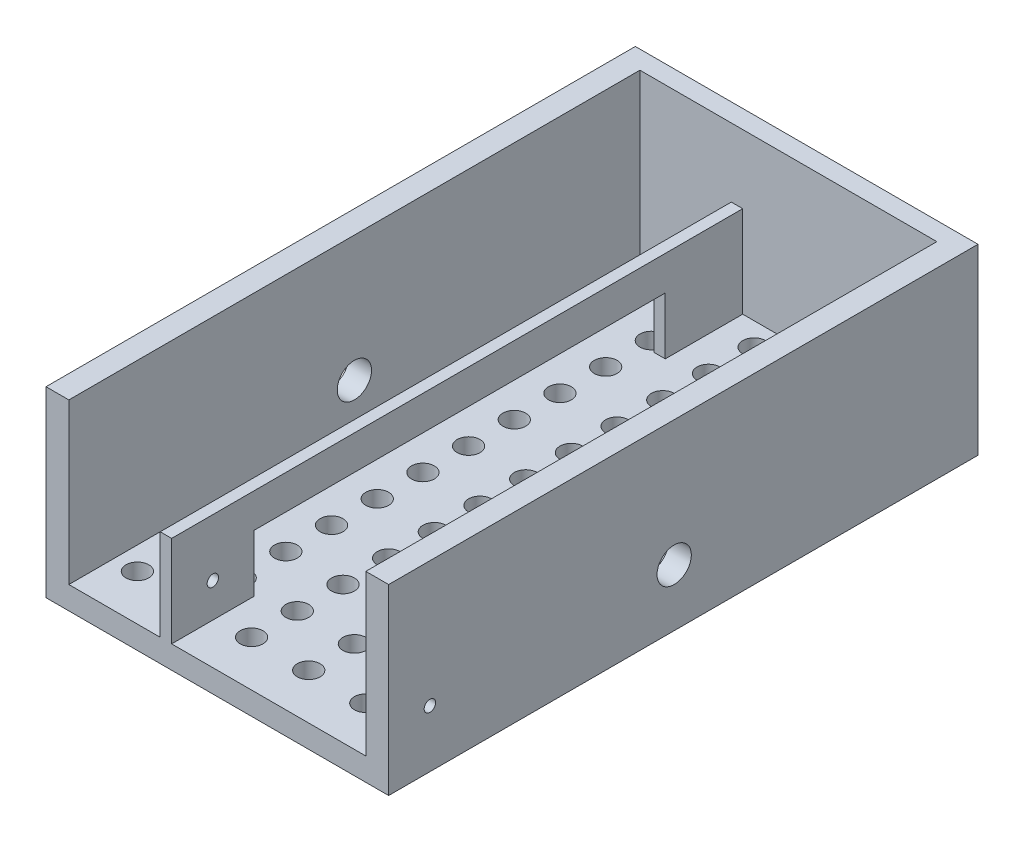
SolidWorks part; units mm, degrees
ref_plane "前基準面" through (0, 0, 0) normal (0, 0, 1) x (1, 0, 0)
ref_plane "上基準面" through (0, 0, 0) normal (0, 1, 0) x (1, 0, 0)
ref_plane "右基準面" through (0, 0, 0) normal (1, 0, 0) x (0, 0, -1)
sketch "草圖4" plane through (0, 0, 0) normal (0, 1, 0) x (1, 0, 0)
  line L1 (-75, 125) -> (75, 125)
  line L2 (-75, 125) -> (-75, -125)
  line L3 (-75, -125) -> (75, -125)
  line L4 (75, 125) -> (75, -125)
  line L5 (-75, 125) -> (75, -125) construction
  line L6 (-75, -125) -> (75, 125) construction
  point P0 (0, 0)
  dimension "D1" = 150
  dimension "D2" = 250
extrude "填料-伸長2" add sketch "草圖4" along normal blind 10
sketch "草圖5" plane through (0, 0, 125) normal (0, 0, 1) x (1, 0, 0)
  line L0 (-75, 0) -> (75, 0) construction
  line L1 (-75, 0) -> (75, 0)
  line L2 (-75, 0) -> (-75, 80)
  line L3 (-75, 80) -> (-65, 80)
  line L4 (-65, 80) -> (-65, 10)
  line L5 (-75, 10) -> (75, 10) construction
  line L6 (-65, 10) -> (-25, 10)
  line L7 (65, 10) -> (65, 80)
  line L8 (65, 80) -> (75, 80)
  line L9 (75, 80) -> (75, 0)
  line L10 (0, -16.5248) -> (0, 113.0975) construction
  line L11 (-20, 10) -> (-20, 50)
  line L12 (-20, 50) -> (-25, 50)
  line L13 (-25, 50) -> (-25, 10)
  line L14 (-20, 10) -> (65, 10)
  dimension "D1" = 10
  dimension "D2" = 80
  dimension "D3" = 5
  dimension "D4" = 40
  dimension "D5" = 85
extrude "填料-伸長3" add sketch "草圖5" against normal up to surface (250 mm away) up to face at (0, 5, -125)
sketch "草圖6" plane through (-25, 0, 0) normal (-1, 0, 0) x (0, 0, 1)
  line L1 (-91.0879, 10) -> (88.9121, 10)
  line L2 (-91.0879, 10) -> (-91.0879, 35)
  line L3 (-91.0879, 35) -> (88.9121, 35)
  line L4 (-125, 50) -> (-125, 10)
  line L5 (-125, 10) -> (125, 10)
  line L6 (125, 10) -> (125, 50)
  line L7 (125, 50) -> (-125, 50)
  line L8 (-125, 50) -> (-125, 10) construction
  line L9 (-125, 10) -> (125, 10) construction
  line L10 (125, 10) -> (125, 50) construction
  line L11 (125, 50) -> (-125, 50) construction
  line L12 (88.9121, 10) -> (88.9121, 35)
  dimension "D2" = 180
  dimension "D3" = 25
  dimension "D1" = 0
extrude "除料-伸長1" cut sketch "草圖6" against normal up to next
sketch "草圖7" plane through (0, 0, -125) normal (0, 0, -1) x (-1, 0, 0)
  line L0 (75, 80) -> (75, 0) construction
  line L1 (-75, 0) -> (75, 0)
  line L2 (-75, 0) -> (-75, 80)
  line L3 (-75, 80) -> (75, 80)
  line L4 (75, 0) -> (75, 80)
  line L6 (-65, 80) -> (-75, 80) construction
extrude "填料-伸長4" add sketch "草圖7" along normal blind 8
sketch "草圖8" plane through (0, 10, 0) normal (0, 1, 0) x (1, 0, 0)
  line L0 (-156.4323, 0) -> (126.5721, 0) construction
  line L1 (-22.5, 91.0879) -> (-22.5, -96.7969) construction
  line L4 (-25, -88.9121) -> (-20, -88.9121)
  line L5 (-25, 91.0879) -> (-25, -88.9121)
  line L6 (-20, 91.0879) -> (-25, 91.0879)
  line L7 (-20, -88.9121) -> (-20, 91.0879)
  line L8 (-25, -88.9121) -> (-20, -88.9121) construction
  line L9 (-25, 91.0879) -> (-25, -88.9121) construction
  line L10 (-20, 91.0879) -> (-25, 91.0879) construction
  line L11 (-20, -88.9121) -> (-20, 91.0879) construction
  circle A0 centre (-22.5, 0) radius 2.5
  point P11 (0, 0)
  dimension "D2" = 5
  dimension "D1" = 0
sketch "草圖9" plane through (-75, 0, 0) normal (-1, 0, 0) x (0, 0, 1)
  line L0 (-133, 40) -> (125, 40) construction
  line L1 (-133, 0) -> (-133, 80) construction
  line L2 (125, 80) -> (125, 0) construction
  line L3 (0, 0) -> (0, 80) construction
  line L4 (-133, 80) -> (125, 80) construction
  line L5 (-133, 0) -> (125, 0) construction
  circle A0 centre (0, 25) radius 7.5
  point P13 (0, 0)
  point P14 (0, 20.6437)
  dimension "D1" = 15
  dimension "D2" = 25
extrude "旋轉軸預留孔" cut sketch "草圖9" against normal through all
sketch "草圖10" plane through (-25, 0, 0) normal (-1, 0, 0) x (0, 0, 1)
  line L0 (106.956, 10) -> (106.956, 80) construction
  line L1 (-133, 80) -> (125, 80) construction
  line L8 (88.9121, 35) -> (88.9121, 10)
  line L9 (88.9121, 10) -> (125, 10)
  line L10 (125, 10) -> (125, 50)
  line L11 (125, 50) -> (-125, 50)
  line L12 (-125, 50) -> (-125, 10)
  line L13 (-125, 10) -> (-91.0879, 10)
  line L14 (-91.0879, 10) -> (-91.0879, 35)
  line L15 (-91.0879, 35) -> (88.9121, 35)
  line L16 (88.9121, 35) -> (88.9121, 10) construction
  line L17 (88.9121, 10) -> (125, 10) construction
  line L18 (125, 10) -> (125, 50) construction
  line L19 (125, 50) -> (-125, 50) construction
  line L20 (-125, 50) -> (-125, 10) construction
  line L21 (-125, 10) -> (-91.0879, 10) construction
  line L22 (-91.0879, 10) -> (-91.0879, 35) construction
  line L23 (-91.0879, 35) -> (88.9121, 35) construction
  circle A0 centre (106.956, 25) radius 2.5
  dimension "D2" = 5
  dimension "D3" = 15
  dimension "D1" = 0
extrude "除料-伸長3" cut sketch "草圖10" against normal through all
sketch "草圖11" plane through (0, 10, 0) normal (0, 1, 0) x (1, 0, 0)
  line L0 (65, 105) -> (65, -145) construction
  line L1 (-65, 125) -> (65, 125) construction
  line L2 (-65, 125) -> (-65, -125) construction
  line L3 (-65, -125) -> (65, -125) construction
  line L4 (65, 125) -> (65, -125) construction
  line L5 (65, 85) -> (65, -165) construction
  line L6 (65, 65) -> (65, -185) construction
  line L7 (65, 45) -> (65, -205) construction
  line L8 (65, 25) -> (65, -225) construction
  line L9 (65, 5) -> (65, -245) construction
  line L10 (65, -15) -> (65, -265) construction
  line L11 (65, -35) -> (65, -285) construction
  line L12 (65, -55) -> (65, -305) construction
  line L13 (65, -75) -> (65, -325) construction
  line L14 (65, -95) -> (65, -345) construction
  circle A0 centre (-55, 115) radius 5
  circle A1 centre (-30, 115) radius 5
  circle A2 centre (-5, 115) radius 5
  circle A3 centre (20, 115) radius 5
  circle A4 centre (45, 115) radius 5
  circle A6 centre (70, 115) radius 5 [skipped]
  circle A7 centre (-55, 95) radius 5
  circle A8 centre (-30, 95) radius 5
  circle A9 centre (-5, 95) radius 5
  circle A10 centre (20, 95) radius 5
  circle A11 centre (45, 95) radius 5
  circle A12 centre (-55, 75) radius 5
  circle A13 centre (-30, 75) radius 5
  circle A14 centre (-5, 75) radius 5
  circle A15 centre (20, 75) radius 5
  circle A16 centre (45, 75) radius 5
  circle A17 centre (-55, 55) radius 5
  circle A18 centre (-30, 55) radius 5
  circle A19 centre (-5, 55) radius 5
  circle A20 centre (20, 55) radius 5
  circle A21 centre (45, 55) radius 5
  circle A22 centre (-55, 35) radius 5
  circle A23 centre (-30, 35) radius 5
  circle A24 centre (-5, 35) radius 5
  circle A25 centre (20, 35) radius 5
  circle A26 centre (45, 35) radius 5
  circle A27 centre (-55, 15) radius 5
  circle A28 centre (-30, 15) radius 5
  circle A29 centre (-5, 15) radius 5
  circle A30 centre (20, 15) radius 5
  circle A31 centre (45, 15) radius 5
  circle A32 centre (-55, -5) radius 5
  circle A33 centre (-30, -5) radius 5
  circle A34 centre (-5, -5) radius 5
  circle A35 centre (20, -5) radius 5
  circle A36 centre (45, -5) radius 5
  circle A37 centre (-55, -25) radius 5
  circle A38 centre (-30, -25) radius 5
  circle A39 centre (-5, -25) radius 5
  circle A40 centre (20, -25) radius 5
  circle A41 centre (45, -25) radius 5
  circle A42 centre (-55, -45) radius 5
  circle A43 centre (-30, -45) radius 5
  circle A44 centre (-5, -45) radius 5
  circle A45 centre (20, -45) radius 5
  circle A46 centre (45, -45) radius 5
  circle A47 centre (-55, -65) radius 5
  circle A48 centre (-30, -65) radius 5
  circle A49 centre (-5, -65) radius 5
  circle A50 centre (20, -65) radius 5
  circle A51 centre (45, -65) radius 5
  circle A52 centre (-55, -85) radius 5
  circle A53 centre (-30, -85) radius 5
  circle A54 centre (-5, -85) radius 5
  circle A55 centre (20, -85) radius 5
  circle A56 centre (45, -85) radius 5
  circle A57 centre (-55, -105) radius 5
  circle A58 centre (-30, -105) radius 5
  circle A59 centre (-5, -105) radius 5
  circle A60 centre (20, -105) radius 5
  circle A61 centre (45, -105) radius 5
  dimension "D1" = 10
  dimension "D2" = 20
  dimension "D3" = 20
  dimension "D5" = 20
  dimension "D6" = 20
  dimension "D8" = 20
  dimension "D4" = 6
  dimension "D7" = 12
extrude "除料-伸長4" cut sketch "草圖11" against normal through all
